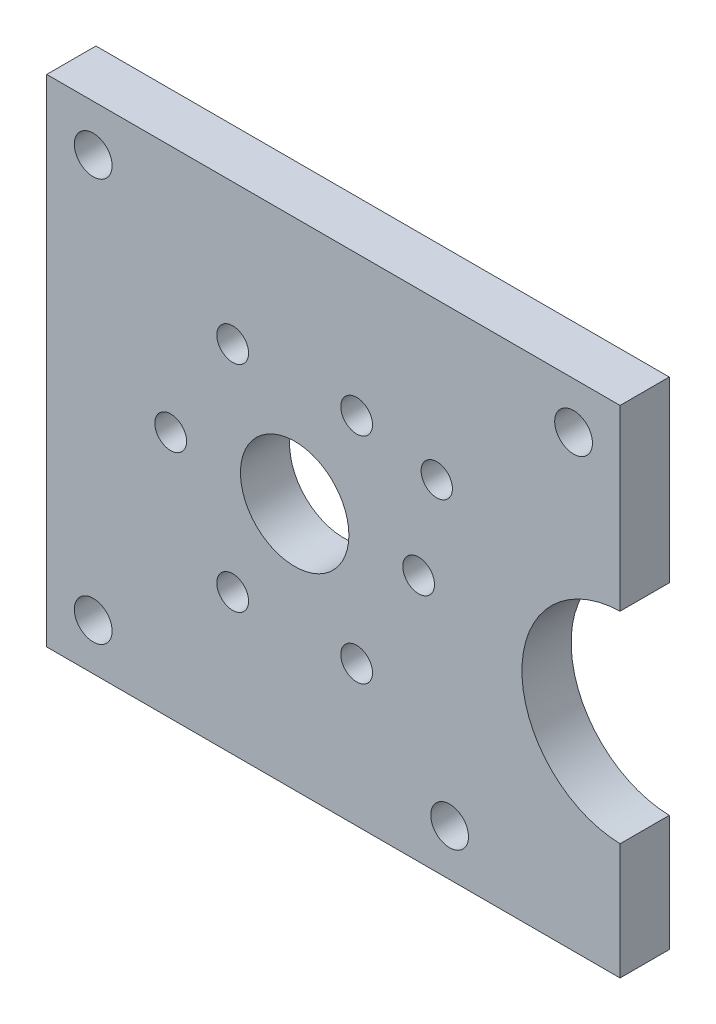
SolidWorks part; units mm, degrees
ref_plane "Front Plane" through (0, 0, 0) normal (0, 0, 1) x (1, 0, 0)
ref_plane "Top Plane" through (0, 0, 0) normal (0, 1, 0) x (1, 0, 0)
ref_plane "Right Plane" through (0, 0, 0) normal (1, 0, 0) x (0, 0, -1)
sketch "Sketch1" plane through (0, 0, 0) normal (0, 0, 1) x (1, 0, 0)
  line L0 (70, 16) -> (0, 16) construction
  line L1 (0, 0) -> (37, 0)
  line L2 (0, 0) -> (0, 32)
  line L3 (0, 32) -> (37, 32)
  line L4 (70, 0) -> (70, 32) construction
  line L5 (16, 25.5) -> (16, 16) construction
  line L6 (37, 32) -> (37, 0) construction
  line L7 (37, 20.4979) -> (37, 32)
  line L8 (37, 7.5021) -> (37, 0)
  line L9 (37, 32) -> (70, 32) construction
  line L10 (37, 0) -> (70, 0) construction
  circle A0 centre (55, 16) radius 2.4892 construction
  circle A1 centre (37.1667, 14) radius 1.4986 construction
  circle A2 centre (25.1698, 21.9334) radius 1.01
  circle A3 centre (37.1667, 14) radius 11.4777 construction
  circle A4 centre (25.1698, 21.9334) radius 7.1501 construction
  circle A5 centre (55, 16) radius 12.827 construction
  circle A6 centre (16, 16) radius 14 construction
  circle A7 centre (37.1667, 14) radius 5.1181 construction
  arc A12 (37, 20.4979) -> (37, 7.5021) centre (37.1667, 14) ccw
  circle A13 centre (16, 16) radius 3.5
  point P7 (55, 16)
  point P8 (37.1667, 14)
  point P9 (25.1698, 21.9334)
  point P19 (16, 16)
  dimension "D6" = 4.9784
  dimension "D7" = 2.9972
  dimension "D8" = 2.02
  dimension "D9" = 25.654
  dimension "D10" = 22.9553
  dimension "D11" = 14.3002
  dimension "D13" = 28
  dimension "D14" = 10.2362
  dimension "D18" = 9.5
  dimension "D20" = 6.5
  dimension "D21" = 7
  dimension "D1" = 17.9451
  dimension "D2" = 14.3828
  dimension "D3" = 32
  dimension "D4" = 70
  dimension "D5" = 15
  dimension "D12" = 10.922
  dimension "D15" = 16
  dimension "D16" = 14
  dimension "D22" = 37
extrude "Boss-Extrude2" add sketch "Sketch1" along normal blind 3.175
hole_wizard "#2 Clearance Hole1" positions "Sketch3" profile "Sketch4" hole size "#2" standard "ANSI Inch"
sketch "Sketch3" plane through (0, 0, 3.175) normal (0, 0, 1) x (1, 0, 0)
  line L0 (3, 32) -> (3, 0) construction
  line L1 (37, 32) -> (0, 32) construction
  line L2 (0, 0) -> (37, 0) construction
  line L4 (34, 32) -> (34, 0) construction
  line L6 (0, 32) -> (0, 0) construction
  line L7 (37, 20.4979) -> (37, 32) construction
  line L8 (3, 3) -> (34, 3) construction
  point P19 (3, 29)
  point P21 (3, 3)
  point P25 (34, 29)
  point P26 (26, 3)
  dimension "D1" = 3
  dimension "D2" = 3
  dimension "D3" = 3
  dimension "D4" = 3
  dimension "D5" = 8
  dimension "D6" = 3
sketch "Sketch4" plane through (3, 29, 3.175) normal (1, 0, 0) x (0, -1, 0)
  line L0 (0, 0) -> (0, 4.0346)
  line L1 (0, 4.0346) -> (1.2192, 3.302)
  line L2 (1.2192, 3.302) -> (1.2192, 0)
  line L5 (1.2192, 0) -> (0, 0)
  line L10 (0, 4.0346) -> (-1.2192, 3.302) construction
  line L11 (0, -6.35) -> (0, 107.95) construction
  dimension "Hole Dia." = 2.4384
  dimension "Hole Depth" = 3.302
  dimension "Drill Angle" = 118
hole_wizard "M2.5x0.45 Tapped Hole1" positions "Sketch6" profile "Sketch5" tap size "M2.5x0.45" standard "ANSI Metric" end condition through all
sketch "Sketch6" plane through (0, 0, 3.175) normal (0, 0, 1) x (1, 0, 0)
  line L1 (0, 16) -> (16, 16) construction
  line L2 (0, 32) -> (0, 0) construction
  point P30 (8, 16)
  point P38 (12, 22.9282)
  point P39 (20, 22.9282)
  point P40 (24, 16)
  point P41 (20, 9.0718)
  point P42 (12, 9.0718)
  point P43 (16, 16)
  dimension "D1" = 8
sketch "Sketch5" plane through (8, 16, 3.175) normal (1, 0, 0) x (0, -1, 0)
  line L0 (0, 0) -> (0, 3.175)
  line L1 (0, 3.175) -> (1.025, 3.175)
  line L2 (1.025, 3.175) -> (1.025, 0)
  line L5 (1.025, 0) -> (0, 0)
  line L11 (0, -6.35) -> (0, 107.95) construction
  dimension "Thru Tap Drill Dia." = 2.05
  dimension "Thru Tap Drill Depth" = 3.175
cosmetic thread "Hole Thread1" parameters "D2"=2.5
cosmetic thread "Hole Thread2" parameters "D2"=2.5
cosmetic thread "Hole Thread3" parameters "D2"=2.5
cosmetic thread "Hole Thread4" parameters "D2"=2.5
cosmetic thread "Hole Thread5" parameters "D2"=2.5
cosmetic thread "Hole Thread6" parameters "D2"=2.5
